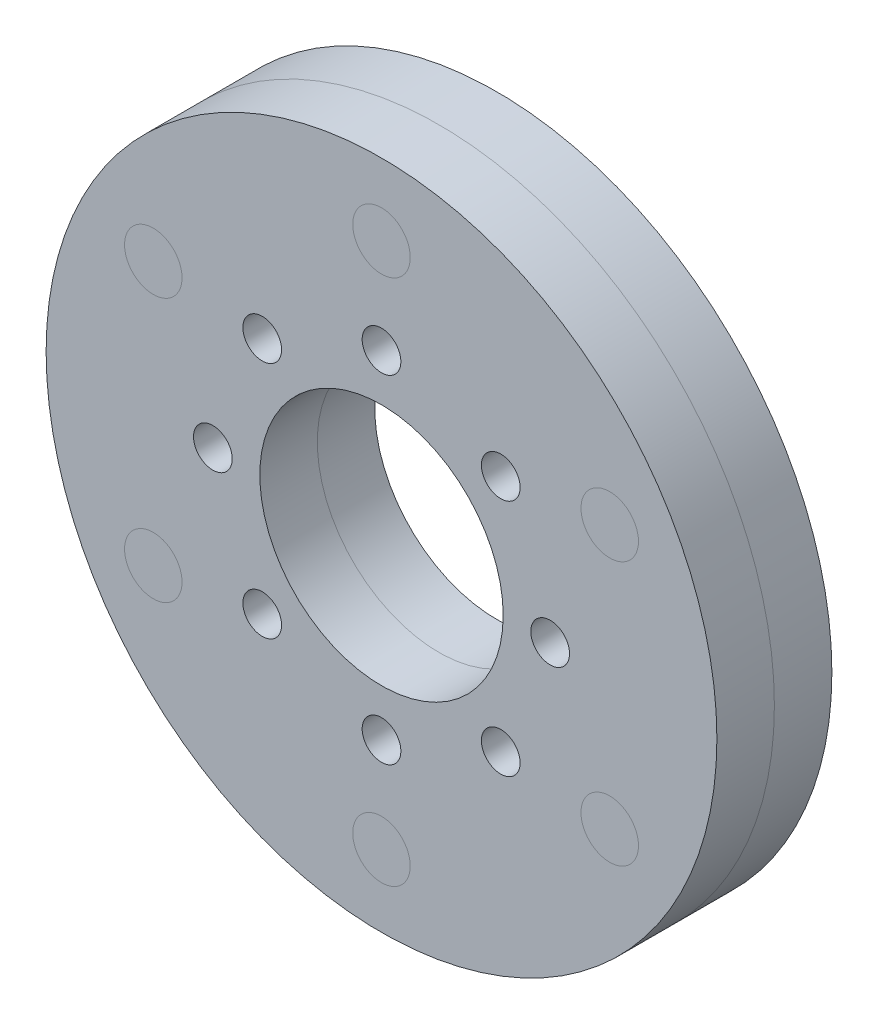
SolidWorks part; units mm, degrees
ref_plane "Front Plane" through (0, 0, 0) normal (0, 0, 1) x (1, 0, 0)
ref_plane "Top Plane" through (0, 0, 0) normal (0, 1, 0) x (1, 0, 0)
ref_plane "Right Plane" through (0, 0, 0) normal (1, 0, 0) x (0, 0, -1)
sketch "Sketch1" plane through (0, 0, 0) normal (0, 0, 1) x (1, 0, 0)
  line L4 (0, 35) -> (0, -35) construction
  circle A0 centre (0, 0) radius 35
  circle A1 centre (0, 27.5) radius 3
  circle A2 centre (23.8157, 13.75) radius 3
  circle A3 centre (23.8157, -13.75) radius 3
  circle A4 centre (0, -27.5) radius 3
  circle A5 centre (-23.8157, -13.75) radius 3
  circle A6 centre (-23.8157, 13.75) radius 3
  point P20 (0, 0)
  point P32 (0, 0)
  dimension "D1" = 70
  dimension "D2" = 6
  dimension "D3" = 27.5
  dimension "D4" = 6
sketch "Sketch2" plane through (0, 0, 0) normal (1, 0, 0) x (0, 0, -1)
  line L0 (-6, 0) -> (6, 0) construction
  line L2 (0, 13.0962) -> (0, -16.405) construction
  dimension "D1" = 6
sketch "Sketch6" plane through (0, 0, 0) normal (0, 0, 1) x (1, 0, 0)
  circle A0 centre (0, 0) radius 35 construction
  circle A1 centre (0, 0) radius 35
  circle A2 centre (0, 27.5) radius 3 construction
  circle A3 centre (23.8157, 13.75) radius 3 construction
  circle A4 centre (23.8157, -13.75) radius 3 construction
  circle A5 centre (0, -27.5) radius 3 construction
  circle A6 centre (-23.8157, -13.75) radius 3 construction
  circle A7 centre (-23.8157, 13.75) radius 3 construction
  circle A10 centre (0, 27.5) radius 3
  circle A11 centre (23.8157, 13.75) radius 3
  circle A12 centre (23.8157, -13.75) radius 3
  circle A13 centre (0, -27.5) radius 3
  circle A14 centre (-23.8157, -13.75) radius 3
  circle A15 centre (-23.8157, 13.75) radius 3
  circle A18 centre (0, 0) radius 27.5 construction
  arc A19 (-6, 26.8375) -> (6, 26.8375) centre (0, 0) cw construction
  arc A20 (7.0909, 31.717) -> (-7.0909, 31.717) centre (0, 0) ccw
  arc A21 (4.9091, 21.9579) -> (-4.9091, 21.9579) centre (0, 0) ccw
  arc A22 (4.9091, 21.9579) -> (7.0909, 31.717) centre (6, 26.8375) ccw
  arc A23 (-7.0909, 31.717) -> (-4.9091, 21.9579) centre (-6, 26.8375) ccw
  arc A24 (20.2419, 18.6149) -> (26.2419, 8.2226) centre (0, 0) cw construction
  arc A25 (31.0132, 9.7176) -> (23.9223, 21.9994) centre (0, 0) ccw
  arc A26 (21.4707, 6.7276) -> (16.5616, 15.2304) centre (0, 0) ccw
  arc A27 (21.4707, 6.7276) -> (31.0132, 9.7176) centre (26.2419, 8.2226) ccw
  arc A28 (23.9223, 21.9994) -> (16.5616, 15.2304) centre (20.2419, 18.6149) ccw
  arc A29 (26.2419, -8.2226) -> (20.2419, -18.6149) centre (0, 0) cw construction
  arc A30 (23.9223, -21.9994) -> (31.0132, -9.7176) centre (0, 0) ccw
  arc A31 (16.5616, -15.2304) -> (21.4707, -6.7276) centre (0, 0) ccw
  arc A32 (16.5616, -15.2304) -> (23.9223, -21.9994) centre (20.2419, -18.6149) ccw
  arc A33 (31.0132, -9.7176) -> (21.4707, -6.7276) centre (26.2419, -8.2226) ccw
  arc A34 (6, -26.8375) -> (-6, -26.8375) centre (0, 0) cw construction
  arc A35 (-7.0909, -31.717) -> (7.0909, -31.717) centre (0, 0) ccw
  arc A36 (-4.9091, -21.9579) -> (4.9091, -21.9579) centre (0, 0) ccw
  arc A37 (-4.9091, -21.9579) -> (-7.0909, -31.717) centre (-6, -26.8375) ccw
  arc A38 (7.0909, -31.717) -> (4.9091, -21.9579) centre (6, -26.8375) ccw
  arc A39 (-20.2419, -18.6149) -> (-26.2419, -8.2226) centre (0, 0) cw construction
  arc A40 (-31.0132, -9.7176) -> (-23.9223, -21.9994) centre (0, 0) ccw
  arc A41 (-21.4707, -6.7276) -> (-16.5616, -15.2304) centre (0, 0) ccw
  arc A42 (-21.4707, -6.7276) -> (-31.0132, -9.7176) centre (-26.2419, -8.2226) ccw
  arc A43 (-23.9223, -21.9994) -> (-16.5616, -15.2304) centre (-20.2419, -18.6149) ccw
  arc A44 (-26.2419, 8.2226) -> (-20.2419, 18.6149) centre (0, 0) cw construction
  arc A45 (-23.9223, 21.9994) -> (-31.0132, 9.7176) centre (0, 0) ccw
  arc A46 (-16.5616, 15.2304) -> (-21.4707, 6.7276) centre (0, 0) ccw
  arc A47 (-16.5616, 15.2304) -> (-23.9223, 21.9994) centre (-20.2419, 18.6149) ccw
  arc A48 (-31.0132, 9.7176) -> (-21.4707, 6.7276) centre (-26.2419, 8.2226) ccw
  point P25 (23.8157, 13.75)
  point P30 (0, 27.5)
  point P41 (23.8157, -13.75)
  point P48 (0, -27.5)
  point P55 (-23.8157, -13.75)
  point P62 (-23.8157, 13.75)
  point P67 (0, 0)
  dimension "D1" = 6
  dimension "D2" = 10
  dimension "D3" = 6
sketch "Sketch9" plane through (0, 0, 0) normal (0, 0, 1) x (1, 0, 0)
  line L0 (0, 35) -> (0, -35) construction
  circle A0 centre (0, 0) radius 12.7
  circle A1 centre (0, 0) radius 9.525 construction
  circle A2 centre (0, 17.6) radius 2.413
  circle A3 centre (12.4451, 12.4451) radius 2.413
  circle A4 centre (17.6, 0) radius 2.413
  circle A5 centre (12.4451, -12.4451) radius 2.413
  circle A6 centre (0, -17.6) radius 2.413
  circle A7 centre (-12.4451, -12.4451) radius 2.413
  circle A8 centre (-17.6, 0) radius 2.413
  circle A9 centre (-12.4451, 12.4451) radius 2.413
  circle A10 centre (-12.4451, 12.4451) radius 3.9751
  point P24 (0, 0)
  dimension "D1" = 25.4
  dimension "D2" = 19.05
  dimension "D3" = 4.826
  dimension "D4" = 17.6
  dimension "D6" = 7.9502
  dimension "D5" = 8
sketch "Sketch4" plane through (0, 0, 0) normal (0, 0, 1) x (1, 0, 0)
  circle A0 centre (-23.8157, 13.75) radius 3 construction
  circle A1 centre (-23.8157, -13.75) radius 3 construction
  circle A2 centre (0, -27.5) radius 3 construction
  circle A3 centre (23.8157, -13.75) radius 3 construction
  circle A4 centre (23.8157, 13.75) radius 3 construction
  circle A5 centre (0, 27.5) radius 3 construction
  circle A8 centre (0, 0) radius 35 construction
  circle A9 centre (-23.8157, 13.75) radius 3
  circle A10 centre (-23.8157, -13.75) radius 3
  circle A11 centre (0, -27.5) radius 3
  circle A12 centre (23.8157, -13.75) radius 3
  circle A13 centre (23.8157, 13.75) radius 3
  circle A14 centre (0, 27.5) radius 3
  circle A17 centre (0, 0) radius 35
extrude "Boss-Extrude3" add sketch "Sketch4" along normal up to vertex (6 mm away) contours A17 A9 A10 A11 A12 A13 A14 region at (0, 0, 0) up to point (0, 0, 6)
extrude "Boss-Extrude4" add sketch "Sketch4<3>" against normal up to vertex (6 mm away) from vertex separate body contours A14 | A13 | A12 | A11 | A10 | A9 region at (-23.8157, 13.75, 0) region at (-23.8157, -13.75, 0) region at (0, -27.5, 0) region at (23.8157, -13.75, 0) region at (23.8157, 13.75, 0) region at (0, 27.5, 0) up to point (0, 0, -6) starting at point (0, 0, 6)
sketch "Sketch4<3>" plane through (0, 0, 0) normal (0, 0, 1) x (1, 0, 0) same geometry as "Sketch4"
sketch "Sketch7" plane through (0, 0, 0) normal (0, 0, 1) x (1, 0, 0)
  circle A1 centre (0, 0) radius 35
  circle A2 centre (0, 0) radius 35
  circle A3 centre (-23.8157, 13.75) radius 3
  circle A4 centre (-23.8157, 13.75) radius 3
  circle A5 centre (-23.8157, -13.75) radius 3
  circle A6 centre (-23.8157, -13.75) radius 3
  circle A7 centre (0, -27.5) radius 3
  circle A8 centre (0, -27.5) radius 3
  circle A9 centre (23.8157, -13.75) radius 3
  circle A10 centre (23.8157, -13.75) radius 3
  circle A11 centre (23.8157, 13.75) radius 3
  circle A12 centre (23.8157, 13.75) radius 3
  circle A13 centre (0, 27.5) radius 3
  circle A14 centre (0, 27.5) radius 3
  arc A18 (23.9223, -21.9994) -> (31.0132, -9.7176) centre (0, 0) ccw
  arc A19 (31.0132, -9.7176) -> (21.4707, -6.7276) centre (26.2419, -8.2226) ccw
  arc A20 (16.5616, -15.2304) -> (21.4707, -6.7276) centre (0, 0) ccw
  arc A21 (16.5616, -15.2304) -> (23.9223, -21.9994) centre (20.2419, -18.6149) ccw
  arc A22 (23.9223, -21.9994) -> (31.0132, -9.7176) centre (0, 0) ccw
  arc A23 (31.0132, -9.7176) -> (21.4707, -6.7276) centre (26.2419, -8.2226) ccw
  arc A24 (16.5616, -15.2304) -> (21.4707, -6.7276) centre (0, 0) ccw
  arc A25 (16.5616, -15.2304) -> (23.9223, -21.9994) centre (20.2419, -18.6149) ccw
  arc A26 (23.9223, 21.9994) -> (16.5616, 15.2304) centre (20.2419, 18.6149) ccw
  arc A27 (21.4707, 6.7276) -> (16.5616, 15.2304) centre (0, 0) ccw
  arc A28 (21.4707, 6.7276) -> (31.0132, 9.7176) centre (26.2419, 8.2226) ccw
  arc A29 (31.0132, 9.7176) -> (23.9223, 21.9994) centre (0, 0) ccw
  arc A30 (23.9223, 21.9994) -> (16.5616, 15.2304) centre (20.2419, 18.6149) ccw
  arc A31 (21.4707, 6.7276) -> (16.5616, 15.2304) centre (0, 0) ccw
  arc A32 (21.4707, 6.7276) -> (31.0132, 9.7176) centre (26.2419, 8.2226) ccw
  arc A33 (31.0132, 9.7176) -> (23.9223, 21.9994) centre (0, 0) ccw
  arc A34 (-7.0909, 31.717) -> (-4.9091, 21.9579) centre (-6, 26.8375) ccw
  arc A35 (4.9091, 21.9579) -> (-4.9091, 21.9579) centre (0, 0) ccw
  arc A36 (4.9091, 21.9579) -> (7.0909, 31.717) centre (6, 26.8375) ccw
  arc A37 (7.0909, 31.717) -> (-7.0909, 31.717) centre (0, 0) ccw
  arc A38 (-7.0909, 31.717) -> (-4.9091, 21.9579) centre (-6, 26.8375) ccw
  arc A39 (4.9091, 21.9579) -> (-4.9091, 21.9579) centre (0, 0) ccw
  arc A40 (4.9091, 21.9579) -> (7.0909, 31.717) centre (6, 26.8375) ccw
  arc A41 (7.0909, 31.717) -> (-7.0909, 31.717) centre (0, 0) ccw
  arc A42 (-31.0132, -9.7176) -> (-23.9223, -21.9994) centre (0, 0) ccw
  arc A43 (-23.9223, -21.9994) -> (-16.5616, -15.2304) centre (-20.2419, -18.6149) ccw
  arc A44 (-21.4707, -6.7276) -> (-16.5616, -15.2304) centre (0, 0) ccw
  arc A45 (-21.4707, -6.7276) -> (-31.0132, -9.7176) centre (-26.2419, -8.2226) ccw
  arc A46 (-31.0132, -9.7176) -> (-23.9223, -21.9994) centre (0, 0) ccw
  arc A47 (-23.9223, -21.9994) -> (-16.5616, -15.2304) centre (-20.2419, -18.6149) ccw
  arc A48 (-21.4707, -6.7276) -> (-16.5616, -15.2304) centre (0, 0) ccw
  arc A49 (-21.4707, -6.7276) -> (-31.0132, -9.7176) centre (-26.2419, -8.2226) ccw
  arc A50 (-7.0909, -31.717) -> (7.0909, -31.717) centre (0, 0) ccw
  arc A51 (7.0909, -31.717) -> (4.9091, -21.9579) centre (6, -26.8375) ccw
  arc A52 (-4.9091, -21.9579) -> (4.9091, -21.9579) centre (0, 0) ccw
  arc A53 (-4.9091, -21.9579) -> (-7.0909, -31.717) centre (-6, -26.8375) ccw
  arc A54 (-7.0909, -31.717) -> (7.0909, -31.717) centre (0, 0) ccw
  arc A55 (7.0909, -31.717) -> (4.9091, -21.9579) centre (6, -26.8375) ccw
  arc A56 (-4.9091, -21.9579) -> (4.9091, -21.9579) centre (0, 0) ccw
  arc A57 (-4.9091, -21.9579) -> (-7.0909, -31.717) centre (-6, -26.8375) ccw
  arc A58 (-31.0132, 9.7176) -> (-21.4707, 6.7276) centre (-26.2419, 8.2226) ccw
  arc A59 (-16.5616, 15.2304) -> (-21.4707, 6.7276) centre (0, 0) ccw
  arc A60 (-16.5616, 15.2304) -> (-23.9223, 21.9994) centre (-20.2419, 18.6149) ccw
  arc A61 (-23.9223, 21.9994) -> (-31.0132, 9.7176) centre (0, 0) ccw
  arc A62 (-31.0132, 9.7176) -> (-21.4707, 6.7276) centre (-26.2419, 8.2226) ccw
  arc A63 (-16.5616, 15.2304) -> (-21.4707, 6.7276) centre (0, 0) ccw
  arc A64 (-16.5616, 15.2304) -> (-23.9223, 21.9994) centre (-20.2419, 18.6149) ccw
  arc A65 (-23.9223, 21.9994) -> (-31.0132, 9.7176) centre (0, 0) ccw
  dimension "D1" = 0
  dimension "D2" = 0
  dimension "D3" = 0
  dimension "D4" = 0
  dimension "D5" = 0
  dimension "D6" = 0
  dimension "D7" = 0
  dimension "D8" = 0
  dimension "D9" = 0
  dimension "D10" = 0
  dimension "D11" = 0
  dimension "D12" = 0
  dimension "D13" = 0
extrude "Boss-Extrude5" add sketch "Sketch7" against normal up to vertex (6 mm away) from vertex separate body contours A2 A65 A64 A63 A62 A57 A56 A55 A54 A49 A48 A47 A46 A41 A40 A39 A38 A33 A32 A31 A30 A25 A24 A23 A22 region at (0, 0, 0) up to point (0, 0, -6) starting at point (0, 0, 0)
sketch "Sketch8" plane through (0, 0, 0) normal (0, 0, 1) x (1, 0, 0)
  circle A0 centre (-23.8157, 13.75) radius 3 construction
  arc A1 (-16.5616, 15.2304) -> (-21.4707, 6.7276) centre (0, 0) ccw construction
  arc A2 (-31.0132, 9.7176) -> (-21.4707, 6.7276) centre (-26.2419, 8.2226) ccw construction
  arc A3 (-23.9223, 21.9994) -> (-31.0132, 9.7176) centre (0, 0) ccw construction
  arc A4 (-16.5616, 15.2304) -> (-23.9223, 21.9994) centre (-20.2419, 18.6149) ccw construction
  circle A5 centre (-23.8157, -13.75) radius 3 construction
  arc A6 (-21.4707, -6.7276) -> (-16.5616, -15.2304) centre (0, 0) ccw construction
  arc A7 (-23.9223, -21.9994) -> (-16.5616, -15.2304) centre (-20.2419, -18.6149) ccw construction
  arc A8 (-31.0132, -9.7176) -> (-23.9223, -21.9994) centre (0, 0) ccw construction
  arc A9 (-21.4707, -6.7276) -> (-31.0132, -9.7176) centre (-26.2419, -8.2226) ccw construction
  arc A10 (-4.9091, -21.9579) -> (4.9091, -21.9579) centre (0, 0) ccw construction
  arc A11 (7.0909, -31.717) -> (4.9091, -21.9579) centre (6, -26.8375) ccw construction
  arc A12 (-7.0909, -31.717) -> (7.0909, -31.717) centre (0, 0) ccw construction
  arc A13 (-4.9091, -21.9579) -> (-7.0909, -31.717) centre (-6, -26.8375) ccw construction
  circle A14 centre (0, -27.5) radius 3 construction
  circle A15 centre (23.8157, -13.75) radius 3 construction
  arc A16 (31.0132, -9.7176) -> (21.4707, -6.7276) centre (26.2419, -8.2226) ccw construction
  arc A17 (16.5616, -15.2304) -> (21.4707, -6.7276) centre (0, 0) ccw construction
  arc A18 (16.5616, -15.2304) -> (23.9223, -21.9994) centre (20.2419, -18.6149) ccw construction
  arc A19 (23.9223, -21.9994) -> (31.0132, -9.7176) centre (0, 0) ccw construction
  circle A20 centre (23.8157, 13.75) radius 3 construction
  arc A21 (23.9223, 21.9994) -> (16.5616, 15.2304) centre (20.2419, 18.6149) ccw construction
  arc A22 (21.4707, 6.7276) -> (16.5616, 15.2304) centre (0, 0) ccw construction
  arc A23 (21.4707, 6.7276) -> (31.0132, 9.7176) centre (26.2419, 8.2226) ccw construction
  arc A24 (31.0132, 9.7176) -> (23.9223, 21.9994) centre (0, 0) ccw construction
  circle A25 centre (0, 27.5) radius 3 construction
  arc A26 (4.9091, 21.9579) -> (7.0909, 31.717) centre (6, 26.8375) ccw construction
  arc A27 (7.0909, 31.717) -> (-7.0909, 31.717) centre (0, 0) ccw construction
  arc A28 (-7.0909, 31.717) -> (-4.9091, 21.9579) centre (-6, 26.8375) ccw construction
  arc A29 (4.9091, 21.9579) -> (-4.9091, 21.9579) centre (0, 0) ccw construction
  circle A30 centre (-23.8157, 13.75) radius 3
  arc A31 (-16.5616, 15.2304) -> (-21.4707, 6.7276) centre (0, 0) ccw
  arc A32 (-31.0132, 9.7176) -> (-21.4707, 6.7276) centre (-26.2419, 8.2226) ccw
  arc A33 (-23.9223, 21.9994) -> (-31.0132, 9.7176) centre (0, 0) ccw
  arc A34 (-16.5616, 15.2304) -> (-23.9223, 21.9994) centre (-20.2419, 18.6149) ccw
  circle A35 centre (-23.8157, -13.75) radius 3
  arc A36 (-21.4707, -6.7276) -> (-16.5616, -15.2304) centre (0, 0) ccw
  arc A37 (-23.9223, -21.9994) -> (-16.5616, -15.2304) centre (-20.2419, -18.6149) ccw
  arc A38 (-31.0132, -9.7176) -> (-23.9223, -21.9994) centre (0, 0) ccw
  arc A39 (-21.4707, -6.7276) -> (-31.0132, -9.7176) centre (-26.2419, -8.2226) ccw
  arc A40 (-4.9091, -21.9579) -> (4.9091, -21.9579) centre (0, 0) ccw
  arc A41 (7.0909, -31.717) -> (4.9091, -21.9579) centre (6, -26.8375) ccw
  arc A42 (-7.0909, -31.717) -> (7.0909, -31.717) centre (0, 0) ccw
  arc A43 (-4.9091, -21.9579) -> (-7.0909, -31.717) centre (-6, -26.8375) ccw
  circle A44 centre (0, -27.5) radius 3
  circle A45 centre (23.8157, -13.75) radius 3
  arc A46 (31.0132, -9.7176) -> (21.4707, -6.7276) centre (26.2419, -8.2226) ccw
  arc A47 (16.5616, -15.2304) -> (21.4707, -6.7276) centre (0, 0) ccw
  arc A48 (16.5616, -15.2304) -> (23.9223, -21.9994) centre (20.2419, -18.6149) ccw
  arc A49 (23.9223, -21.9994) -> (31.0132, -9.7176) centre (0, 0) ccw
  circle A50 centre (23.8157, 13.75) radius 3
  arc A51 (23.9223, 21.9994) -> (16.5616, 15.2304) centre (20.2419, 18.6149) ccw
  arc A52 (21.4707, 6.7276) -> (16.5616, 15.2304) centre (0, 0) ccw
  arc A53 (21.4707, 6.7276) -> (31.0132, 9.7176) centre (26.2419, 8.2226) ccw
  arc A54 (31.0132, 9.7176) -> (23.9223, 21.9994) centre (0, 0) ccw
  circle A55 centre (0, 27.5) radius 3
  arc A56 (4.9091, 21.9579) -> (7.0909, 31.717) centre (6, 26.8375) ccw
  arc A57 (7.0909, 31.717) -> (-7.0909, 31.717) centre (0, 0) ccw
  arc A58 (-7.0909, 31.717) -> (-4.9091, 21.9579) centre (-6, 26.8375) ccw
  arc A59 (4.9091, 21.9579) -> (-4.9091, 21.9579) centre (0, 0) ccw
extrude "Boss-Extrude6" add sketch "Sketch8" against normal up to vertex (6 mm away) from vertex separate body up to point (0, 0, -6) starting at point (0, 0, 0)
hole_wizard "#10-32 Tapped Hole1" positions "Sketch10" profile "Sketch11" tap size "#10-32" standard "ANSI Inch" end condition through all
sketch "Sketch10" plane through (0, 0, 6) normal (0, 0, 1) x (1, 0, 0)
  point P0 (-12.4451, 12.4451)
  point P3 (0, 17.6)
  point P6 (12.4451, 12.4451)
  point P9 (17.6, 0)
  point P12 (12.4451, -12.4451)
  point P15 (0, -17.6)
  point P18 (-12.4451, -12.4451)
  point P21 (-17.6, 0)
sketch "Sketch11" plane through (-12.4451, 12.4451, 6) normal (1, 0, 0) x (0, -1, 0)
  line L0 (0, 0) -> (0, 12)
  line L1 (0, 12) -> (2.0193, 12)
  line L2 (2.0193, 12) -> (2.0193, 0)
  line L5 (2.0193, 0) -> (0, 0)
  line L11 (0, -6.35) -> (0, 107.95) construction
  dimension "Thru Tap Drill Dia." = 4.0386
  dimension "Thru Tap Drill Depth" = 12
cosmetic thread "Hole Thread1" parameters "D2"=4.826
cosmetic thread "Hole Thread2" parameters "D2"=4.826
cosmetic thread "Hole Thread3" parameters "D2"=4.826
cosmetic thread "Hole Thread4" parameters "D2"=4.826
cosmetic thread "Hole Thread5" parameters "D2"=4.826
cosmetic thread "Hole Thread6" parameters "D2"=4.826
cosmetic thread "Hole Thread7" parameters "D2"=4.826
cosmetic thread "Hole Thread8" parameters "D2"=4.826
sketch "Sketch12" plane through (0, 0, 0) normal (0, 0, 1) x (1, 0, 0)
  circle A0 centre (0, 0) radius 12.7 construction
  circle A1 centre (0, 0) radius 12.7
extrude "Cut-Extrude1" cut sketch "Sketch12" against normal through all both and the other way through all
hole_wizard "#10-32 Tapped Hole2" positions "Sketch13" profile "Sketch14" tap size "#10-32" standard "ANSI Inch"
sketch "Sketch13" plane through (0, 0, -6) normal (0, 0, -1) x (-1, 0, 0)
  point P0 (0, 17.6)
  point P3 (12.4451, 12.4451)
  point P6 (17.6, 0)
  point P9 (12.4451, -12.4451)
  point P12 (0, -17.6)
  point P15 (-12.4451, -12.4451)
  point P18 (-17.6, 0)
  point P21 (-12.4451, 12.4451)
sketch "Sketch14" plane through (0, 17.6, -6) normal (1, 0, 0) x (0, 1, 0)
  line L0 (0, 0) -> (0, 13.2433)
  line L1 (0, 13.2433) -> (2.0193, 12.03)
  line L2 (2.0193, 12.03) -> (2.0193, 0)
  line L5 (2.0193, 0) -> (0, 0)
  line L10 (0, 13.2433) -> (-2.0193, 12.03) construction
  line L11 (0, -6.35) -> (0, 107.95) construction
  dimension "Tap Drill Dia." = 4.0386
  dimension "Tap Drill Depth" = 12.03
  dimension "Drill Angle" = 118
